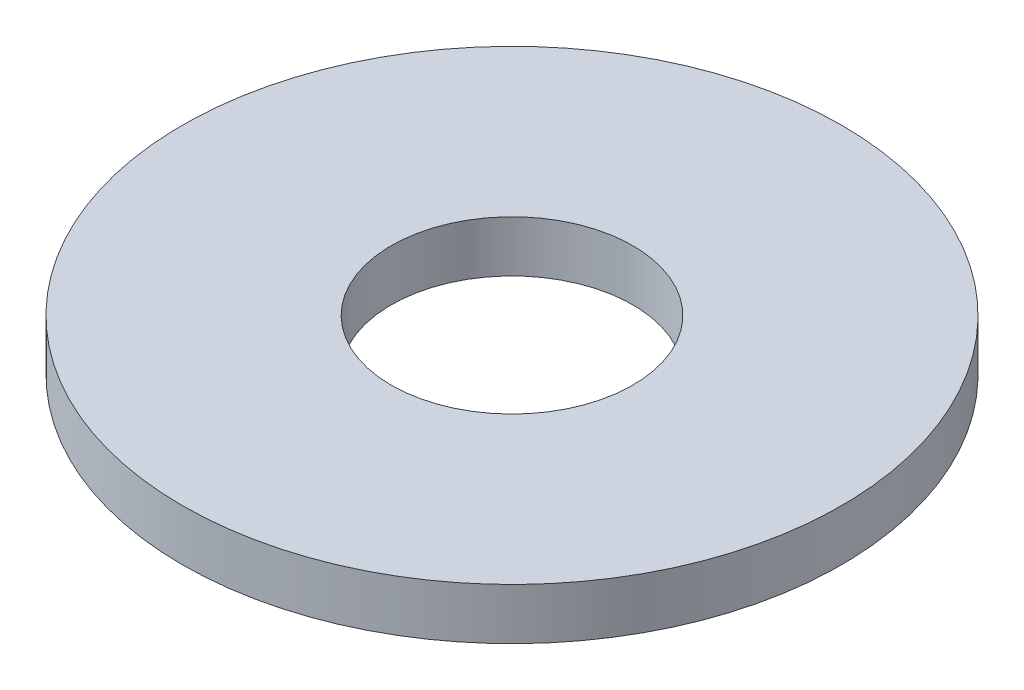
SolidWorks part; units mm, degrees
ref_plane "Front Plane" through (0, 0, 0) normal (0, 0, 1) x (1, 0, 0)
ref_plane "Top Plane" through (0, 0, 0) normal (0, 1, 0) x (1, 0, 0)
ref_plane "Right Plane" through (0, 0, 0) normal (1, 0, 0) x (0, 0, -1)
sketch "Sketch1" plane through (0, 0, 0) normal (0, 1, 0) x (1, 0, 0)
  circle A0 centre (0, 0) radius 4.5
  circle A1 centre (0, 0) radius 1.65
  dimension "D1" = 9
  dimension "D2" = 3.3
extrude "Boss-Extrude1" add sketch "Sketch1" along normal blind 0.7
